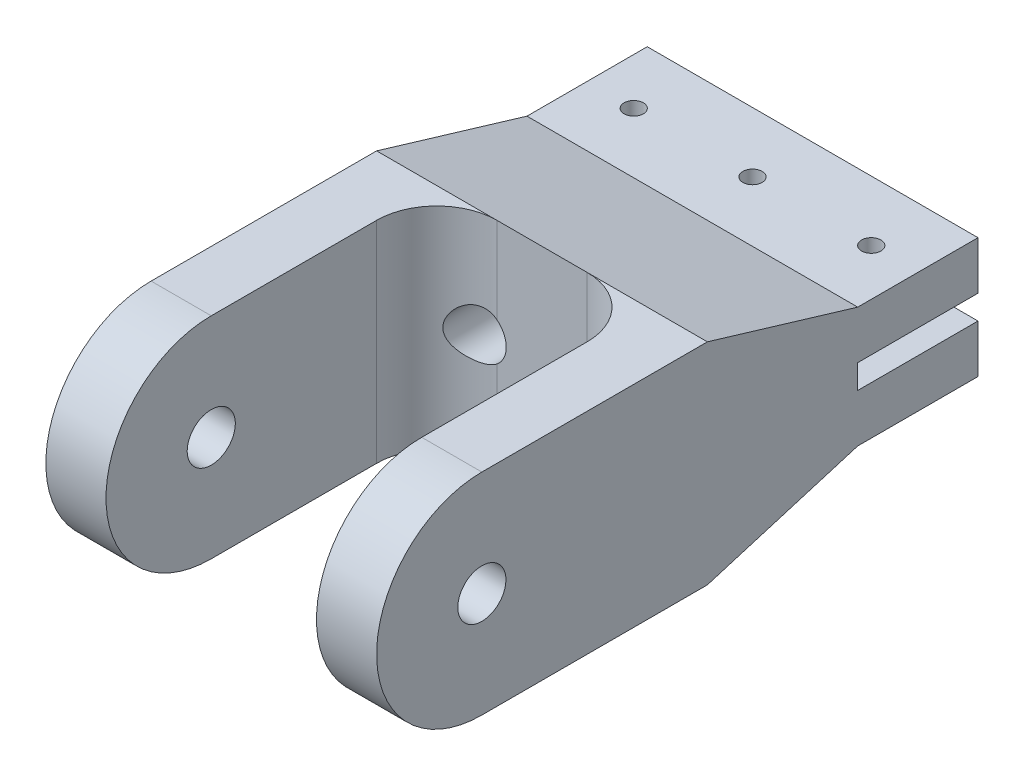
SolidWorks part; units mm, degrees
ref_plane "Alzado" through (0, 0, 0) normal (0, 0, 1) x (1, 0, 0)
ref_plane "Planta" through (0, 0, 0) normal (0, 1, 0) x (1, 0, 0)
ref_plane "Vista lateral" through (0, 0, 0) normal (1, 0, 0) x (0, 0, -1)
sketch "Croquis1" plane through (0, 0, 0) normal (0, 0, 1) x (1, 0, 0)
  line L1 (-27.5, -17.5) -> (27.5, -17.5)
  line L2 (-27.5, -17.5) -> (-27.5, 17.5)
  line L3 (-27.5, 17.5) -> (27.5, 17.5)
  line L4 (27.5, -17.5) -> (27.5, 17.5)
  line L5 (-27.5, -17.5) -> (27.5, 17.5) construction
  line L6 (-27.5, 17.5) -> (27.5, -17.5) construction
  point P0 (0, 0)
extrude "Saliente-Extruir1" add sketch "Croquis1" along normal blind 100
sketch "Croquis2" plane through (27.5, 0, 0) normal (1, 0, 0) x (0, 0, -1)
  line L0 (-100, 0) -> (-45, 0) construction
  line L1 (-100, -17.5) -> (-100, 17.5) construction
  line L2 (-45, 17.5) -> (-45, -17.5) construction
  line L3 (-100, 17.5) -> (0, 17.5) construction
  line L4 (-100, -17.5) -> (0, -17.5) construction
  line L5 (-100, 4.9186) -> (-82.5, 4.9186) construction
  line L6 (-82.5, 17.5) -> (-100, 17.5)
  line L7 (-100, 17.5) -> (-100, 0)
  line L8 (-100, 0) -> (-100, -17.5)
  line L9 (-100, -17.5) -> (-82.5, -17.5)
  circle A2 centre (-82.5, 0) radius 4
  circle A3 centre (-82.5, 0) radius 17.5
  line M3 (0, 17.5) -> (-100, 17.5)
  line M4 (-100, 17.5) -> (-100, -17.5)
  line M5 (-100, -17.5) -> (0, -17.5)
extrude "Cortar-Extruir1" cut sketch "Croquis2" against normal blind 100 contours A2 | A3 M3 M4 | A3 M4 M5 region at (27.5, 13.5911, 96.0911) region at (27.5, -13.5911, 96.0911) region at (27.5, 0, 82.5)
sketch "Croquis3" plane through (0, 17.5, 0) normal (0, 1, 0) x (1, 0, 0)
  line L0 (0, -100) -> (0, -45) construction
  line L1 (-27.5, -100) -> (27.5, -100) construction
  line L2 (-27.5, -45) -> (-17.5, -45) construction
  line L3 (-27.5, -82.5) -> (-27.5, 0) construction
  line L4 (27.5, -45) -> (17.5, -45) construction
  line L5 (27.5, -82.5) -> (27.5, 0) construction
  line L7 (17.5, -45) -> (-17.5, -45)
  line L8 (17.5, -45) -> (17.5, -100)
  line L9 (17.5, -100) -> (-17.5, -100)
  line L10 (-17.5, -45) -> (-17.5, -100)
extrude "Cortar-Extruir2" cut sketch "Croquis3" against normal blind 39
sketch "Croquis6" plane through (27.5, 0, 0) normal (1, 0, 0) x (0, 0, -1)
  line L0 (0, 0) -> (0, 10) construction
  line L2 (0, -17.5) -> (0, 17.5) construction
  line L3 (0, 0) -> (0, -10) construction
  line L4 (0, 10) -> (-20, 10) construction
  line L5 (0, -10) -> (-20, -10) construction
  line L6 (-100, 0) -> (-45, 0) construction
  line L7 (-45, 17.5) -> (-20, 10) construction
  line L8 (-20, -10) -> (-45, -17.5) construction
  line L9 (-82.5, -17.5) -> (0, -17.5) construction
  line L10 (0, 0) -> (-20, 0) construction
  line L11 (-20, 0) -> (-20, 2) construction
  line L12 (-20, 0) -> (-20, -2) construction
  line L13 (-45, 17.5) -> (0, 17.5)
  line L14 (-20, 2) -> (0, 2)
  line L15 (-20, 2) -> (-20, -2)
  line L16 (-20, -2) -> (0, -2)
  line L17 (0, 2) -> (0, -2)
  line L18 (0, 17.5) -> (0, 10)
  line L19 (0, 10) -> (-20, 10)
  line L20 (-20, 10) -> (-45, 17.5)
  line L21 (-45, -17.5) -> (-20, -10)
  line L22 (-20, -10) -> (0, -10)
  line L23 (0, -10) -> (0, -17.5)
  line L24 (0, -17.5) -> (-45, -17.5)
  arc A0 (-82.5, 17.5) -> (-82.5, -17.5) centre (-82.5, 0) ccw construction
extrude "Cortar-Extruir3" cut sketch "Croquis6" against normal blind 55
sketch "Croquis7" plane through (0, 0, 0) normal (0, 0, -1) x (-1, 0, 0)
  line L0 (0, 10) -> (0, -10) construction
  line L1 (27.5, 10) -> (-27.5, 10) construction
  line L2 (27.5, -10) -> (-27.5, -10) construction
  line L3 (0, 0) -> (10, 0) construction
  line L4 (0, 0) -> (-10, 0) construction
  circle A0 centre (-10, 0) radius 4.05
  circle A1 centre (10, 0) radius 4.05
extrude "Cortar-Extruir4" cut sketch "Croquis7" against normal blind 55
fillet "Redondeo1" radius 10 1 edges at (-17.5, 0, 45) type face fillet first side face at (-17.5, 0, 86.5) second side face at (5.95, 0, 45)
fillet "Redondeo2" radius 10 1 edges at (17.5, 0, 45) type face fillet first side face at (5.95, 0, 45) second side face at (17.5, 0, 78.5)
sketch "Croquis8" plane through (0, 10, 0) normal (0, 1, 0) x (1, 0, 0)
  line L0 (0, 0) -> (0, -20) construction
  line L1 (-27.5, -20) -> (27.5, -20) construction
  line L2 (0, -10) -> (12, -10) construction
  line L3 (12, -10) -> (27.5, -10) construction
  line L4 (27.5, -20) -> (27.5, 0) construction
  line L5 (0, -10) -> (-12, -10) construction
  line L6 (-12, -10) -> (-27.5, -10) construction
  line L7 (-27.5, -20) -> (-27.5, 0) construction
  circle A0 centre (0, -10) radius 1.6
  circle A1 centre (-19.75, -10) radius 1.6
  circle A2 centre (19.75, -10) radius 1.6
extrude "Cortar-Extruir5" cut sketch "Croquis8" against normal blind 20
